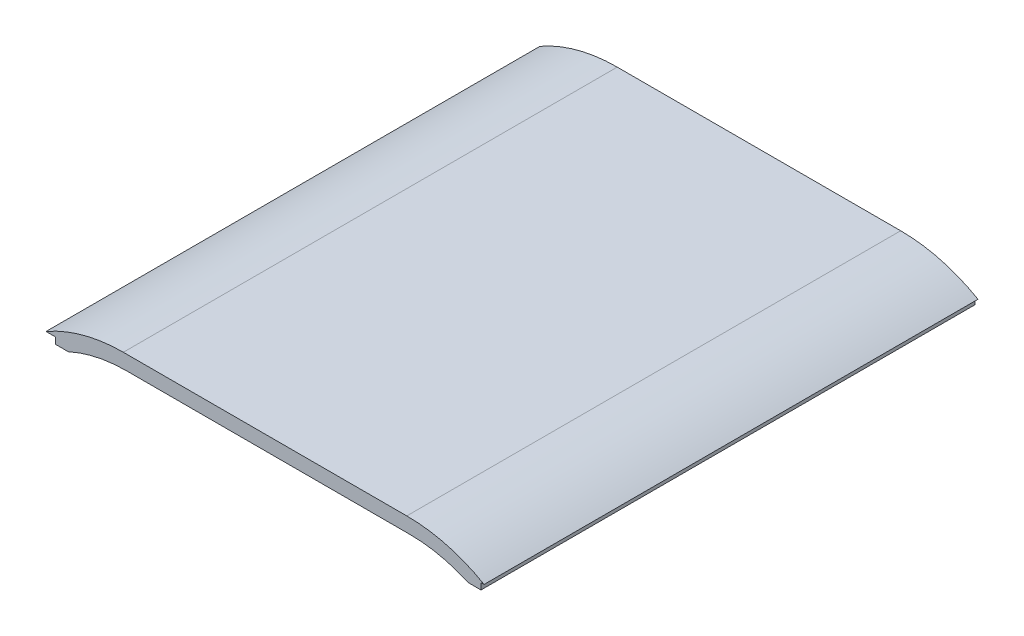
SolidWorks part; units mm, degrees
material "that blue high density foam"
ref_plane "Front" through (0, 0, 0) normal (0, 0, 1) x (1, 0, 0)
ref_plane "Top" through (0, 0, 0) normal (0, 1, 0) x (1, 0, 0)
ref_plane "Right" through (0, 0, 0) normal (1, 0, 0) x (0, 0, -1)
sketch "Sketch1" plane through (0, 0, 0) normal (0, 0, 1) x (1, 0, 0)
  line L1 (-70.0714, 162.1134) -> (67.0955, 162.1134)
  line L2 (-107.488, 152.1134) -> (-103, 152.1134)
  line L4 (-68.5834, 155.1134) -> (68.5834, 155.1134)
  line L5 (-96.7213, 149.0187) -> (-96.7213, 149.0187)
  line L6 (103, 152.1134) -> (104.512, 152.1134)
  line L7 (-96.7213, 149.0187) -> (-103, 149.0187)
  line L9 (-103, 149.0187) -> (-103, 152.1134)
  line L13 (0, 169.0467) -> (0, 139.3264) construction
  line L14 (96.7213, 149.0187) -> (103, 149.0187)
  line L15 (103, 149.0187) -> (103, 152.1134)
  arc A0 (-70.0714, 162.1134) -> (-107.488, 152.1134) centre (-70.0714, 87.1134) ccw construction
  arc A1 (-70.0714, 162.1134) -> (-107.488, 152.1134) centre (-70.0714, 87.1134) ccw
  arc A2 (104.512, 152.1134) -> (67.0955, 162.1134) centre (67.0955, 87.1134) ccw construction
  arc A3 (104.512, 152.1134) -> (67.0955, 162.1134) centre (67.0955, 87.1134) ccw
  arc A5 (-68.5834, 155.1134) -> (-96.7213, 149.0187) centre (-68.5834, 87.1134) ccw
  arc A6 (102.5078, 146.0468) -> (68.5834, 155.1134) centre (68.5834, 87.1134) ccw construction
  arc A7 (68.5834, 155.1134) -> (96.7213, 149.0187) centre (68.5834, 87.1134) cw
  dimension "D1" = 7
extrude "Boss-Extrude1" add sketch "Sketch1" along normal up to surface (239 mm away) contours A5 L4 L6 A3 L1 A1 L2 L9 L7 region at (-1.929, 157.7037, 0)
